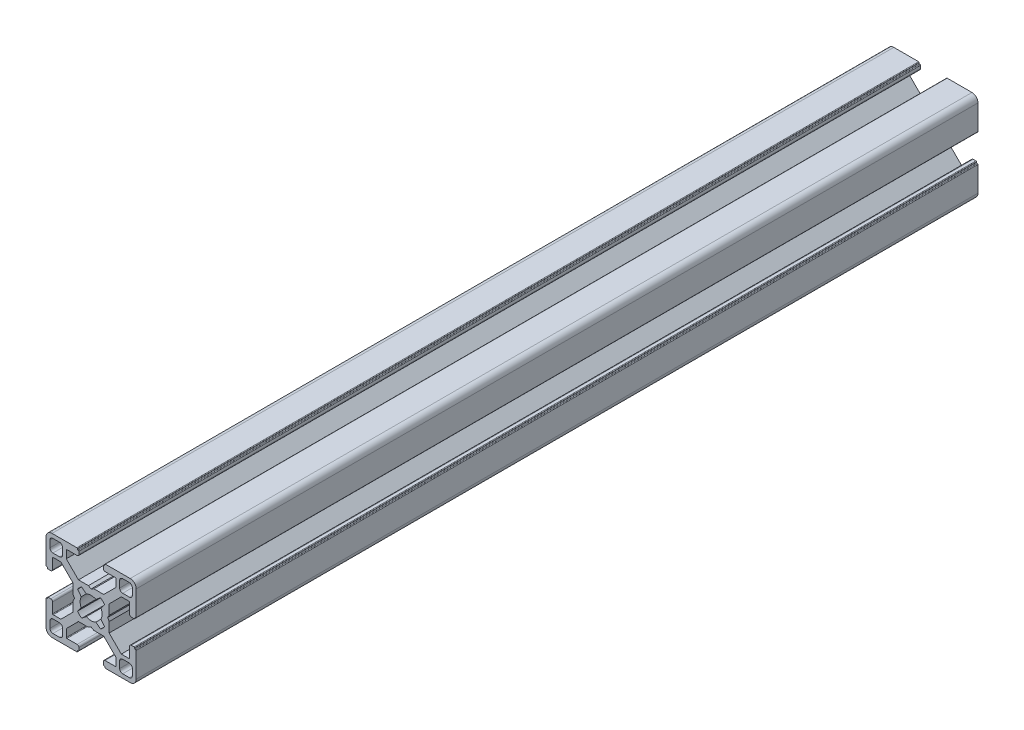
SolidWorks part; units mm, degrees
ref_plane "Płaszczyzna przednia" through (0, 0, 0) normal (0, 0, 1) x (1, 0, 0)
ref_plane "Płaszczyzna górna" through (0, 0, 0) normal (0, 1, 0) x (1, 0, 0)
ref_plane "Płaszczyzna prawa" through (0, 0, 0) normal (1, 0, 0) x (0, 0, -1)
sketch "Szkic1" plane through (0, 0, 0) normal (0, 0, 1) x (1, 0, 0)
  line L0 (109.26, 48.76) -> (107.06, 48.76)
  line L1 (106.06, 47.76) -> (106.06, 45.56)
  line L2 (107.06, 44.56) -> (109.26, 44.56)
  line L3 (110.26, 45.56) -> (110.26, 47.76)
  line L4 (94.9599, 38.3406) -> (93.4241, 39.5784)
  line L5 (92.0547, 38.2147) -> (93.2794, 36.6601)
  line L6 (93.2794, 33.4599) -> (92.0547, 31.9053)
  line L7 (93.4241, 30.5416) -> (94.9599, 31.7794)
  line L8 (98.1601, 31.7794) -> (99.6959, 30.5416)
  line L9 (101.0653, 31.9053) -> (99.8406, 33.4599)
  line L10 (99.8406, 36.6601) -> (101.0653, 38.2147)
  line L11 (99.6959, 39.5784) -> (98.1601, 38.3406)
  line L12 (83.86, 21.36) -> (86.06, 21.36)
  line L13 (87.06, 22.36) -> (87.06, 24.56)
  line L14 (86.06, 25.56) -> (83.86, 25.56)
  line L15 (82.86, 24.56) -> (82.86, 22.36)
  line L16 (110.26, 22.36) -> (110.26, 24.56)
  line L17 (109.26, 25.56) -> (107.06, 25.56)
  line L18 (106.06, 24.56) -> (106.06, 22.36)
  line L19 (86.06, 48.76) -> (83.86, 48.76)
  line L20 (82.86, 47.76) -> (82.86, 45.56)
  line L21 (83.86, 44.56) -> (86.06, 44.56)
  line L22 (87.06, 45.56) -> (87.06, 47.76)
  line L23 (107.06, 21.36) -> (109.26, 21.36)
  line L24 (96.56, 29.5751) -> (97.46, 29.06)
  line L25 (97.46, 29.06) -> (100.7645, 29.06)
  line L26 (100.7645, 29.06) -> (104.81, 25.01)
  line L27 (104.81, 25.01) -> (104.81, 22.46)
  line L28 (104.61, 22.26) -> (101.21, 22.26)
  line L29 (100.61, 21.66) -> (100.61, 20.76)
  line L30 (100.81, 20.56) -> (100.91, 20.56)
  line L31 (101.11, 20.36) -> (101.11, 20.26)
  line L32 (101.31, 20.06) -> (109.56, 20.06)
  line L33 (111.56, 22.06) -> (111.56, 30.31)
  line L34 (111.36, 30.51) -> (111.26, 30.51)
  line L35 (111.06, 30.71) -> (111.06, 30.81)
  line L36 (110.86, 31.01) -> (109.96, 31.01)
  line L37 (109.36, 30.41) -> (109.36, 27.01)
  line L38 (109.16, 26.81) -> (106.61, 26.81)
  line L39 (106.61, 26.81) -> (102.5645, 30.8555)
  line L40 (102.5645, 30.8555) -> (102.5645, 34.16)
  line L41 (102.5645, 34.16) -> (102.0449, 35.06)
  line L42 (102.0449, 35.06) -> (102.5645, 35.96)
  line L43 (102.5645, 35.96) -> (102.5645, 39.2645)
  line L44 (102.5645, 39.2645) -> (106.61, 43.31)
  line L45 (106.61, 43.31) -> (109.16, 43.31)
  line L46 (109.36, 43.11) -> (109.36, 39.71)
  line L47 (109.96, 39.11) -> (110.86, 39.11)
  line L48 (111.06, 39.31) -> (111.06, 39.41)
  line L49 (111.26, 39.61) -> (111.36, 39.61)
  line L50 (111.56, 39.81) -> (111.56, 48.06)
  line L51 (109.56, 50.06) -> (101.31, 50.06)
  line L52 (101.11, 49.86) -> (101.11, 49.76)
  line L53 (100.91, 49.56) -> (100.81, 49.56)
  line L54 (100.61, 49.36) -> (100.61, 48.46)
  line L55 (101.21, 47.86) -> (104.61, 47.86)
  line L56 (104.81, 47.66) -> (104.81, 45.11)
  line L57 (104.81, 45.11) -> (100.7645, 41.06)
  line L58 (100.7645, 41.06) -> (97.46, 41.06)
  line L59 (97.46, 41.06) -> (96.56, 40.5449)
  line L60 (96.56, 40.5449) -> (95.66, 41.06)
  line L61 (95.66, 41.06) -> (92.3555, 41.06)
  line L62 (92.3555, 41.06) -> (88.31, 45.11)
  line L63 (88.31, 45.11) -> (88.31, 47.66)
  line L64 (88.51, 47.86) -> (91.91, 47.86)
  line L65 (92.51, 48.46) -> (92.51, 49.36)
  line L66 (92.31, 49.56) -> (92.21, 49.56)
  line L67 (92.01, 49.76) -> (92.01, 49.86)
  line L68 (91.81, 50.06) -> (83.56, 50.06)
  line L69 (81.56, 48.06) -> (81.56, 39.81)
  line L70 (81.76, 39.61) -> (81.86, 39.61)
  line L71 (82.06, 39.41) -> (82.06, 39.31)
  line L72 (82.26, 39.11) -> (83.16, 39.11)
  line L73 (83.76, 39.71) -> (83.76, 43.11)
  line L74 (83.96, 43.31) -> (86.51, 43.31)
  line L75 (86.51, 43.31) -> (90.5555, 39.2645)
  line L76 (90.5555, 39.2645) -> (90.5555, 35.96)
  line L77 (90.5555, 35.96) -> (91.0751, 35.06)
  line L78 (91.0751, 35.06) -> (90.5555, 34.16)
  line L79 (90.5555, 34.16) -> (90.5555, 30.8555)
  line L80 (90.5555, 30.8555) -> (86.51, 26.81)
  line L81 (86.51, 26.81) -> (83.96, 26.81)
  line L82 (83.76, 27.01) -> (83.76, 30.41)
  line L83 (83.16, 31.01) -> (82.26, 31.01)
  line L84 (82.06, 30.81) -> (82.06, 30.71)
  line L85 (81.86, 30.51) -> (81.76, 30.51)
  line L86 (81.56, 30.31) -> (81.56, 22.06)
  line L87 (83.56, 20.06) -> (91.81, 20.06)
  line L88 (92.01, 20.26) -> (92.01, 20.36)
  line L89 (92.21, 20.56) -> (92.31, 20.56)
  line L90 (92.51, 20.76) -> (92.51, 21.66)
  line L91 (91.91, 22.26) -> (88.51, 22.26)
  line L92 (88.31, 22.46) -> (88.31, 25.01)
  line L93 (88.31, 25.01) -> (92.3555, 29.06)
  line L94 (92.3555, 29.06) -> (95.66, 29.06)
  line L95 (95.66, 29.06) -> (96.56, 29.5751)
  arc A0 (107.06, 48.76) -> (106.06, 47.76) centre (107.06, 47.76) ccw
  arc A1 (106.06, 45.56) -> (107.06, 44.56) centre (107.06, 45.56) ccw
  arc A2 (109.26, 44.56) -> (110.26, 45.56) centre (109.26, 45.56) ccw
  arc A3 (110.26, 47.76) -> (109.26, 48.76) centre (109.26, 47.76) ccw
  arc A4 (93.4241, 39.5784) -> (92.0547, 38.2147) centre (96.56, 35.06) ccw
  arc A5 (93.2794, 36.6601) -> (93.2794, 33.4599) centre (96.56, 35.06) ccw
  arc A6 (92.0547, 31.9053) -> (93.4241, 30.5416) centre (96.56, 35.06) ccw
  arc A7 (94.9599, 31.7794) -> (98.1601, 31.7794) centre (96.56, 35.06) ccw
  arc A8 (99.6959, 30.5416) -> (101.0653, 31.9053) centre (96.56, 35.06) ccw
  arc A9 (99.8406, 33.4599) -> (99.8406, 36.6601) centre (96.56, 35.06) ccw
  arc A10 (101.0653, 38.2147) -> (99.6959, 39.5784) centre (96.56, 35.06) ccw
  arc A11 (98.1601, 38.3406) -> (94.9599, 38.3406) centre (96.56, 35.06) ccw
  arc A12 (86.06, 21.36) -> (87.06, 22.36) centre (86.06, 22.36) ccw
  arc A13 (87.06, 24.56) -> (86.06, 25.56) centre (86.06, 24.56) ccw
  arc A14 (83.86, 25.56) -> (82.86, 24.56) centre (83.86, 24.56) ccw
  arc A15 (82.86, 22.36) -> (83.86, 21.36) centre (83.86, 22.36) ccw
  arc A16 (109.26, 21.36) -> (110.26, 22.36) centre (109.26, 22.36) ccw
  arc A17 (110.26, 24.56) -> (109.26, 25.56) centre (109.26, 24.56) ccw
  arc A18 (107.06, 25.56) -> (106.06, 24.56) centre (107.06, 24.56) ccw
  arc A19 (106.06, 22.36) -> (107.06, 21.36) centre (107.06, 22.36) ccw
  arc A20 (83.86, 48.76) -> (82.86, 47.76) centre (83.86, 47.76) ccw
  arc A21 (82.86, 45.56) -> (83.86, 44.56) centre (83.86, 45.56) ccw
  arc A22 (86.06, 44.56) -> (87.06, 45.56) centre (86.06, 45.56) ccw
  arc A23 (87.06, 47.76) -> (86.06, 48.76) centre (86.06, 47.76) ccw
  arc A24 (104.61, 22.26) -> (104.81, 22.46) centre (104.61, 22.46) ccw
  arc A25 (101.21, 22.26) -> (100.61, 21.66) centre (101.21, 21.66) ccw
  arc A26 (100.61, 20.76) -> (100.81, 20.56) centre (100.81, 20.76) ccw
  arc A27 (101.11, 20.36) -> (100.91, 20.56) centre (100.91, 20.36) ccw
  arc A28 (101.11, 20.26) -> (101.31, 20.06) centre (101.31, 20.26) ccw
  arc A29 (109.56, 20.06) -> (111.56, 22.06) centre (109.56, 22.06) ccw
  arc A30 (111.56, 30.31) -> (111.36, 30.51) centre (111.36, 30.31) ccw
  arc A31 (111.06, 30.71) -> (111.26, 30.51) centre (111.26, 30.71) ccw
  arc A32 (111.06, 30.81) -> (110.86, 31.01) centre (110.86, 30.81) ccw
  arc A33 (109.96, 31.01) -> (109.36, 30.41) centre (109.96, 30.41) ccw
  arc A34 (109.16, 26.81) -> (109.36, 27.01) centre (109.16, 27.01) ccw
  arc A35 (109.36, 43.11) -> (109.16, 43.31) centre (109.16, 43.11) ccw
  arc A36 (109.36, 39.71) -> (109.96, 39.11) centre (109.96, 39.71) ccw
  arc A37 (110.86, 39.11) -> (111.06, 39.31) centre (110.86, 39.31) ccw
  arc A38 (111.26, 39.61) -> (111.06, 39.41) centre (111.26, 39.41) ccw
  arc A39 (111.36, 39.61) -> (111.56, 39.81) centre (111.36, 39.81) ccw
  arc A40 (111.56, 48.06) -> (109.56, 50.06) centre (109.56, 48.06) ccw
  arc A41 (101.31, 50.06) -> (101.11, 49.86) centre (101.31, 49.86) ccw
  arc A42 (100.91, 49.56) -> (101.11, 49.76) centre (100.91, 49.76) ccw
  arc A43 (100.81, 49.56) -> (100.61, 49.36) centre (100.81, 49.36) ccw
  arc A44 (100.61, 48.46) -> (101.21, 47.86) centre (101.21, 48.46) ccw
  arc A45 (104.81, 47.66) -> (104.61, 47.86) centre (104.61, 47.66) ccw
  arc A46 (88.51, 47.86) -> (88.31, 47.66) centre (88.51, 47.66) ccw
  arc A47 (91.91, 47.86) -> (92.51, 48.46) centre (91.91, 48.46) ccw
  arc A48 (92.51, 49.36) -> (92.31, 49.56) centre (92.31, 49.36) ccw
  arc A49 (92.01, 49.76) -> (92.21, 49.56) centre (92.21, 49.76) ccw
  arc A50 (92.01, 49.86) -> (91.81, 50.06) centre (91.81, 49.86) ccw
  arc A51 (83.56, 50.06) -> (81.56, 48.06) centre (83.56, 48.06) ccw
  arc A52 (81.56, 39.81) -> (81.76, 39.61) centre (81.76, 39.81) ccw
  arc A53 (82.06, 39.41) -> (81.86, 39.61) centre (81.86, 39.41) ccw
  arc A54 (82.06, 39.31) -> (82.26, 39.11) centre (82.26, 39.31) ccw
  arc A55 (83.16, 39.11) -> (83.76, 39.71) centre (83.16, 39.71) ccw
  arc A56 (83.96, 43.31) -> (83.76, 43.11) centre (83.96, 43.11) ccw
  arc A57 (83.76, 27.01) -> (83.96, 26.81) centre (83.96, 27.01) ccw
  arc A58 (83.76, 30.41) -> (83.16, 31.01) centre (83.16, 30.41) ccw
  arc A59 (82.26, 31.01) -> (82.06, 30.81) centre (82.26, 30.81) ccw
  arc A60 (81.86, 30.51) -> (82.06, 30.71) centre (81.86, 30.71) ccw
  arc A61 (81.76, 30.51) -> (81.56, 30.31) centre (81.76, 30.31) ccw
  arc A62 (81.56, 22.06) -> (83.56, 20.06) centre (83.56, 22.06) ccw
  arc A63 (91.81, 20.06) -> (92.01, 20.26) centre (91.81, 20.26) ccw
  arc A64 (92.21, 20.56) -> (92.01, 20.36) centre (92.21, 20.36) ccw
  arc A65 (92.31, 20.56) -> (92.51, 20.76) centre (92.31, 20.76) ccw
  arc A66 (92.51, 21.66) -> (91.91, 22.26) centre (91.91, 21.66) ccw
  arc A67 (88.31, 22.46) -> (88.51, 22.26) centre (88.51, 22.46) ccw
  dimension "D1" = 3.65
  dimension "D2" = 30
  dimension "D3" = 30
  dimension "D4" = 8.1
extrude "Dodanie-wyciągnięcie1" add sketch "Szkic1" along normal blind 280
